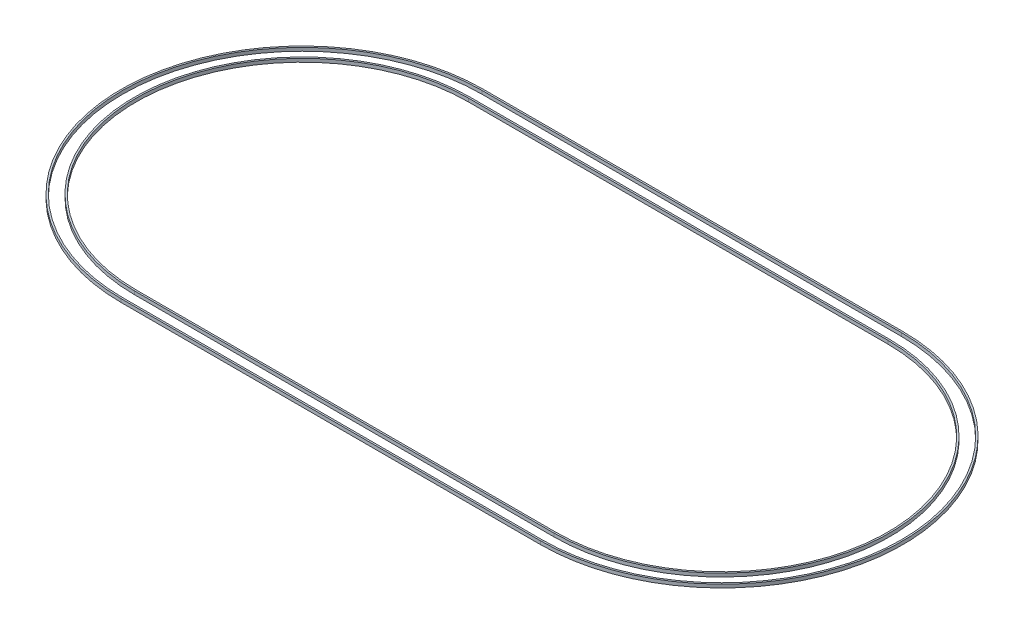
SolidWorks part; units mm, degrees
ref_plane "Front Plane" through (0, 0, 0) normal (0, 0, 1) x (1, 0, 0)
ref_plane "Top Plane" through (0, 0, 0) normal (0, 1, 0) x (1, 0, 0)
ref_plane "Right Plane" through (0, 0, 0) normal (1, 0, 0) x (0, 0, -1)
sketch "Sketch1" plane through (0, 0, 0) normal (0, 1, 0) x (1, 0, 0)
  line L0 (-25000, -20000) -> (25000, -20000)
  line L1 (-25000, 20000) -> (25000, 20000)
  line L2 (-25000, -20000) -> (-25000, 20000) construction
  line L3 (25000, -20000) -> (25000, 20000) construction
  line L4 (-25000, -19800) -> (25000, -19800)
  line L5 (-25000, 19800) -> (25000, 19800)
  line L6 (-25000, -21400) -> (25000, -21400)
  line L7 (-25000, 21400) -> (25000, 21400)
  line L8 (-25000, -21600) -> (25000, -21600)
  line L9 (-25000, 21600) -> (25000, 21600)
  arc A0 (-25000, 20000) -> (-25000, -20000) centre (-25000, 0) ccw
  arc A1 (25000, 20000) -> (25000, -20000) centre (25000, 0) cw
  arc A2 (25000, 19800) -> (25000, -19800) centre (25000, 0) cw
  arc A3 (-25000, 19800) -> (-25000, -19800) centre (-25000, 0) ccw
  arc A4 (25000, 21400) -> (25000, -21400) centre (25000, 0) cw
  arc A5 (-25000, 21400) -> (-25000, -21400) centre (-25000, 0) ccw
  arc A6 (25000, 21600) -> (25000, -21600) centre (25000, 0) cw
  arc A7 (-25000, 21600) -> (-25000, -21600) centre (-25000, 0) ccw
  dimension "D6" = 1400
  dimension "D7" = 200
  dimension "D1" = 50000
  dimension "D2" = 40000
  dimension "D4" = 25000
  dimension "D5" = 200
  dimension "D3" = 0
extrude "Boss-Extrude1" add sketch "Sketch1" along normal blind 400 contours A1 L1 A0 L0 A3 L5 A2 L4 region at (-44901.5114, 0, 0)
extrude "Boss-Extrude2" add sketch "Sketch1<6>" along normal blind 400 separate body contours A5 L6 A4 L7 | A7 L8 A6 L9
sketch "Sketch1<6>" plane through (0, 0, 0) normal (0, 1, 0) x (1, 0, 0) same geometry as "Sketch1"
